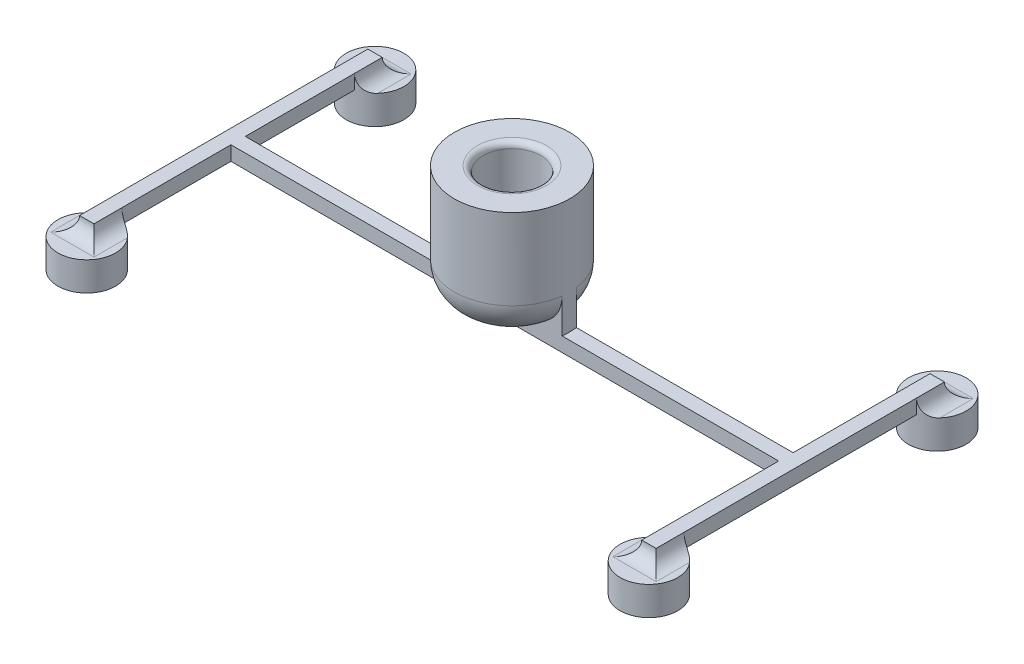
SolidWorks part; units mm, degrees
ref_plane "Ebene vorne" through (0, 0, 0) normal (0, 0, 1) x (1, 0, 0)
ref_plane "Ebene oben" through (0, 0, 0) normal (0, 1, 0) x (1, 0, 0)
ref_plane "Ebene rechts" through (0, 0, 0) normal (1, 0, 0) x (0, 0, -1)
sketch "Skizze2" plane through (0, 0, 0) normal (0, 1, 0) x (1, 0, 0)
  line L1 (-50, -100) -> (50, -100)
  line L2 (-50, -100) -> (-50, 100)
  line L3 (-50, 100) -> (50, 100)
  line L4 (50, -100) -> (50, 100)
  line L5 (-50, -100) -> (50, 100) construction
  line L6 (-50, 100) -> (50, -100) construction
  circle A0 centre (0, 0) radius 20
  point P0 (0, 0)
  dimension "D3" = 40
  dimension "D1" = 100
  dimension "D2" = 200
extrude "Aufsatz-Linear austragen1" add sketch "Skizze2" along normal blind 40 contours A0
sketch "Skizze5" plane through (0, 0, 0) normal (0, -1, 0) x (1, 0, 0)
  line L3 (-2.5, 2.5) -> (-46.25, 2.5)
  line L7 (-51.25, 2.5) -> (-95, 2.5)
  line L8 (-95, 2.5) -> (-95, 50)
  line L9 (-95, 50) -> (-100, 50)
  line L10 (-100, 50) -> (-100, -50)
  line L11 (-100, 0) -> (0, 0) construction
  line L13 (-2.5, -2.5) -> (-46.25, -2.5)
  line L16 (-51.25, -2.5) -> (-95, -2.5)
  line L17 (-95, -2.5) -> (-95, -50)
  line L18 (-95, -50) -> (-100, -50)
  line L39 (-46.25, -2.5) -> (-51.25, -2.5)
  line L40 (-46.25, 2.5) -> (-51.25, 2.5)
  line L41 (0, 0) -> (0, 59.7641) construction
  line L42 (2.5, -2.5) -> (46.25, -2.5)
  line L43 (2.5, 2.5) -> (46.25, 2.5)
  line L44 (46.25, -2.5) -> (51.25, -2.5)
  line L45 (46.25, 2.5) -> (51.25, 2.5)
  line L46 (51.25, 2.5) -> (95, 2.5)
  line L47 (51.25, -2.5) -> (95, -2.5)
  line L48 (95, -2.5) -> (95, -50)
  line L49 (95, -50) -> (100, -50)
  line L50 (95, 50) -> (100, 50)
  line L51 (100, 50) -> (100, -50)
  line L52 (95, 2.5) -> (95, 50)
  line L53 (-2.5, 2.5) -> (2.5, 2.5)
  line L54 (-2.5, -2.5) -> (2.5, -2.5)
  dimension "D1" = 100
  dimension "D4" = 5
  dimension "D5" = 50
  dimension "D6" = 2.5
  dimension "D7" = 2.5
extrude "Aufsatz-Linear austragen2" add sketch "Skizze5" along normal blind 5
sketch "Skizze8" plane through (0, 40, 0) normal (0, 1, 0) x (1, 0, 0)
  circle A0 centre (0, 0) radius 10
  dimension "D1" = 20
extrude "Schnitt-Linear austragen1" cut sketch "Skizze8" against normal blind 35
fillet "Verrundung1" radius 2 1 edges at (0, 40, 10)
fillet "Verrundung2" radius 12 2 edges at (0, 0, -20) (0, 0, 20)
sketch "Skizze9" plane through (0, -5, 0) normal (0, -1, 0) x (1, 0, 0)
  line L0 (-95, 50) -> (-100, 50) construction
  line L1 (-100, -50) -> (-95, -50) construction
  line L2 (100, 50) -> (95, 50) construction
  line L3 (95, -50) -> (100, -50) construction
  circle A0 centre (-97.5, 50) radius 10
  circle A1 centre (-97.5, -50) radius 10
  circle A2 centre (97.5, 50) radius 10
  circle A3 centre (97.5, -50) radius 10
  dimension "D1" = 20
  dimension "D2" = 20
  dimension "D3" = 20
  dimension "D4" = 20
extrude "Aufsatz-Linear austragen3" add sketch "Skizze9" along normal blind 10
fillet "Verrundung3" radius 5 3 edges at (95, -5, -45.1588) (97.5, -5, -50) (100, -5, -45.1588)
fillet "Verrundung4" radius 5 3 edges at (97.5, -5, 50) (95, -5, 45.1588) (100, -5, 45.1588)
fillet "Verrundung5" radius 5 3 edges at (-95, -5, 45.1588) (-97.5, -5, 50) (-100, -5, 45.1588)
fillet "Verrundung6" radius 5 3 edges at (-100, -5, -45.1588) (-97.5, -5, -50) (-95, -5, -45.1588)
